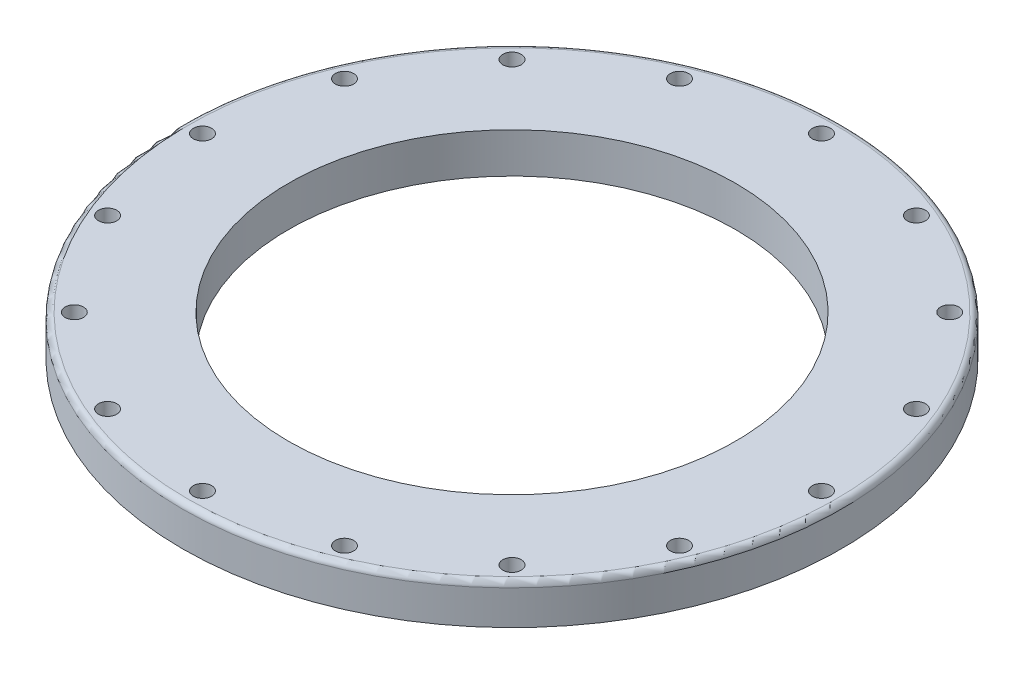
SolidWorks part; units mm, degrees
ref_plane "Front Plane" through (0, 0, 0) normal (0, 0, 1) x (1, 0, 0)
ref_plane "Top Plane" through (0, 0, 0) normal (0, 1, 0) x (1, 0, 0)
ref_plane "Right Plane" through (0, 0, 0) normal (1, 0, 0) x (0, 0, -1)
sketch "Sketch1" plane through (0, 0, 0) normal (0, 1, 0) x (1, 0, 0)
  circle A0 centre (0, 0) radius 57.5
  circle A1 centre (0, 0) radius 39
  dimension "D1" = 78
  dimension "D2" = 115
extrude "Boss-Extrude1" add sketch "Sketch1" along normal blind 7
sketch "Sketch2" plane through (0, 7, 0) normal (0, 1, 0) x (1, 0, 0)
  circle A0 centre (0, 0) radius 54 construction
  circle A1 centre (0, 54) radius 1.6
  circle A2 centre (20.6649, 49.8895) radius 1.6
  circle A3 centre (38.1838, 38.1838) radius 1.6
  circle A4 centre (49.8895, 20.6649) radius 1.6
  circle A5 centre (54, 0) radius 1.6
  circle A6 centre (49.8895, -20.6649) radius 1.6
  circle A7 centre (38.1838, -38.1838) radius 1.6
  circle A8 centre (20.6649, -49.8895) radius 1.6
  circle A9 centre (0, -54) radius 1.6
  circle A10 centre (-20.6649, -49.8895) radius 1.6
  circle A11 centre (-38.1838, -38.1838) radius 1.6
  circle A12 centre (-49.8895, -20.6649) radius 1.6
  circle A13 centre (-54, 0) radius 1.6
  circle A14 centre (-49.8895, 20.6649) radius 1.6
  circle A15 centre (-38.1838, 38.1838) radius 1.6
  circle A16 centre (-20.6649, 49.8895) radius 1.6
  point P37 (0, 0)
  dimension "D1" = 108
  dimension "D2" = 3.2
  dimension "D3" = 16
extrude "Cut-Extrude1" cut sketch "Sketch2" against normal blind 25
fillet "Fillet1" radius 1 1 edges at (0, 7, 57.5)
